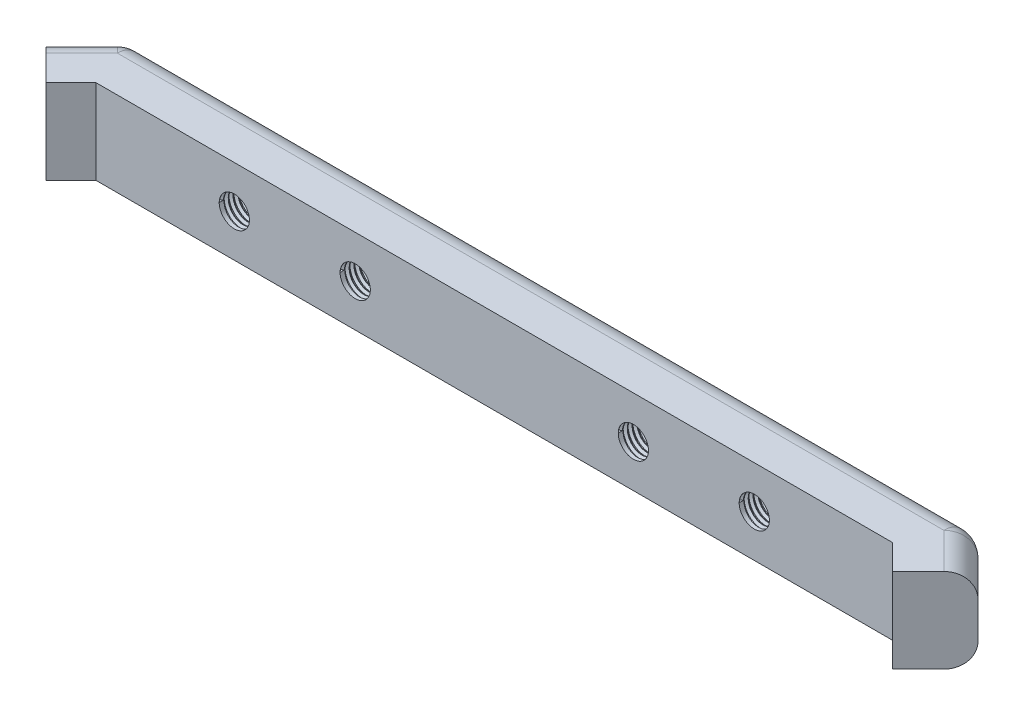
SolidWorks part; units mm, degrees
ref_plane "Front Plane" through (0, 0, 0) normal (0, 0, 1) x (1, 0, 0)
ref_plane "Top Plane" through (0, 0, 0) normal (0, 1, 0) x (1, 0, 0)
ref_plane "Right Plane" through (0, 0, 0) normal (1, 0, 0) x (0, 0, -1)
sketch "Sketch1" plane through (0, 0, 0) normal (0, 1, 0) x (1, 0, 0)
  line L0 (-350, 46.9737) -> (350, 46.9737)
  line L1 (-350, 46.9737) -> (-385.3553, 11.6184)
  line L2 (-385.3553, 11.6184) -> (-350, -23.737)
  line L3 (-350, -23.737) -> (-329.2893, -3.0263)
  line L4 (-329.2893, -3.0263) -> (329.2893, -3.0263)
  line L5 (329.2893, -3.0263) -> (350, -23.737)
  line L6 (350, -23.737) -> (385.3553, 11.6184)
  line L7 (385.3553, 11.6184) -> (350, 46.9737)
  line L8 (0, 166.9334) -> (0, -42.6279) construction
  line L9 (0, 0) -> (0, 199.6316) construction
  point P3 (0, 46.9737)
  dimension "D1" = 700
  dimension "D2" = 135
  dimension "D3" = 135
  dimension "D4" = 50
  dimension "D5" = 50
  dimension "D6" = 50
  dimension "D7" = 50
  dimension "D8" = 50
  dimension "D9" = 0
extrude "Boss-Extrude1" add sketch "Sketch1" along normal blind 70
fillet "Fillet1" radius 20 1 edges at (350, 35, -46.9737)
fillet "Fillet2" radius 20 1 edges at (-350, 35, -46.9737)
fillet "Fillet3" radius 20 10 edges at (370.6066, 70, -26.3671) (349.3694, 70, -45.4513) (-370.6066, 70, -26.3671) (-349.3694, 70, -45.4513) (370.6066, 0, -26.3671) (349.3694, 0, -45.4513) (-370.6066, 0, -26.3671) (-349.3694, 0, -45.4513) (0, 70, -46.9737) (0, 0, -46.9737)
sketch "Sketch2" plane through (0, 0, 3.0263) normal (0, 0, 1) x (1, 0, 0)
  line L0 (0, 240.313) -> (0, -306.3994) construction
  line L1 (552.822, 35) -> (-733.9228, 35) construction
  line L2 (-329.2893, 70) -> (329.2893, 70) construction
  line L3 (-329.2893, 0) -> (329.2893, 0) construction
  line L5 (-165, 240.313) -> (-165, -377.1142) construction
  line L9 (165, 240.313) -> (165, -401.4016) construction
  circle A0 centre (-215, 35) radius 12.5
  circle A2 centre (-115, 35) radius 12.5
  circle A3 centre (215, 35) radius 12.5
  circle A4 centre (115, 35) radius 12.5
  dimension "D3" = 25
  dimension "D4" = 50
  dimension "D5" = 25
  dimension "D1" = 165
  dimension "D2" = 165
  dimension "D6" = 50
extrude "Cut-Extrude1" cut sketch "Sketch2" against normal blind 25
thread "Thread1" pitch 4 method cut profile "Thread Profile1" start angle 0, offset 0, length 0, pitch 4, diameter 25
ref_plane "Plane1" through (102.5, 35, 3.0263) normal (0, 1, 0) x (1, 0, 0)
sketch "Thread Profile1" plane through (102.5, 35, 3.0263) normal (0, 1, 0) x (1, 0, 0)
  line L0 (0, 0) -> (0, 4) construction
  line L11 (0, 0) -> (0, 3.5)
  line L12 (0, 3.5) -> (-2.1651, 2.25)
  line L13 (-2.1651, 2.25) -> (-2.1651, 1.25)
  line L15 (-2.1651, 1.25) -> (0, 0)
  line L17 (-2.1651, 1.75) -> (0, 1.75) construction
  point P2 (0, 0)
  dimension "Pitch" = 4
  dimension "Profile_Angle" = 60
  dimension "Profile_Land" = 1
  dimension "Profile_Height" = 2.1651
thread "Thread2" pitch 4 method cut profile "Thread Profile2" start angle 0, offset 0, length 0, pitch 4, diameter 25
ref_plane "Plane2" through (202.5, 35, 3.0263) normal (0, 1, 0) x (1, 0, 0)
sketch "Thread Profile2" plane through (202.5, 35, 3.0263) normal (0, 1, 0) x (1, 0, 0)
  line L0 (0, 0) -> (0, 4) construction
  line L11 (0, 0) -> (0, 3.5)
  line L12 (0, 3.5) -> (-2.1651, 2.25)
  line L13 (-2.1651, 2.25) -> (-2.1651, 1.25)
  line L15 (-2.1651, 1.25) -> (0, 0)
  line L17 (-2.1651, 1.75) -> (0, 1.75) construction
  point P2 (0, 0)
  dimension "Pitch" = 4
  dimension "Profile_Angle" = 60
  dimension "Profile_Land" = 1
  dimension "Profile_Height" = 2.1651
thread "Thread3" pitch 4 method cut profile "Thread Profile3" start angle 0, offset 0, length 0, pitch 4, diameter 25
ref_plane "Plane3" through (-127.5, 35, 3.0263) normal (0, 1, 0) x (1, 0, 0)
sketch "Thread Profile3" plane through (-127.5, 35, 3.0263) normal (0, 1, 0) x (1, 0, 0)
  line L0 (0, 0) -> (0, 4) construction
  line L11 (0, 0) -> (0, 3.5)
  line L12 (0, 3.5) -> (-2.1651, 2.25)
  line L13 (-2.1651, 2.25) -> (-2.1651, 1.25)
  line L15 (-2.1651, 1.25) -> (0, 0)
  line L17 (-2.1651, 1.75) -> (0, 1.75) construction
  point P2 (0, 0)
  dimension "Pitch" = 4
  dimension "Profile_Angle" = 60
  dimension "Profile_Land" = 1
  dimension "Profile_Height" = 2.1651
thread "Thread4" pitch 4 method cut profile "Thread Profile4" start angle 0, offset 0, length 0, pitch 4, diameter 25
ref_plane "Plane4" through (-227.5, 35, 3.0263) normal (0, 1, 0) x (1, 0, 0)
sketch "Thread Profile4" plane through (-227.5, 35, 3.0263) normal (0, 1, 0) x (1, 0, 0)
  line L0 (0, 0) -> (0, 4) construction
  line L11 (0, 0) -> (0, 3.5)
  line L12 (0, 3.5) -> (-2.1651, 2.25)
  line L13 (-2.1651, 2.25) -> (-2.1651, 1.25)
  line L15 (-2.1651, 1.25) -> (0, 0)
  line L17 (-2.1651, 1.75) -> (0, 1.75) construction
  point P2 (0, 0)
  dimension "Pitch" = 4
  dimension "Profile_Angle" = 60
  dimension "Profile_Land" = 1
  dimension "Profile_Height" = 2.1651
